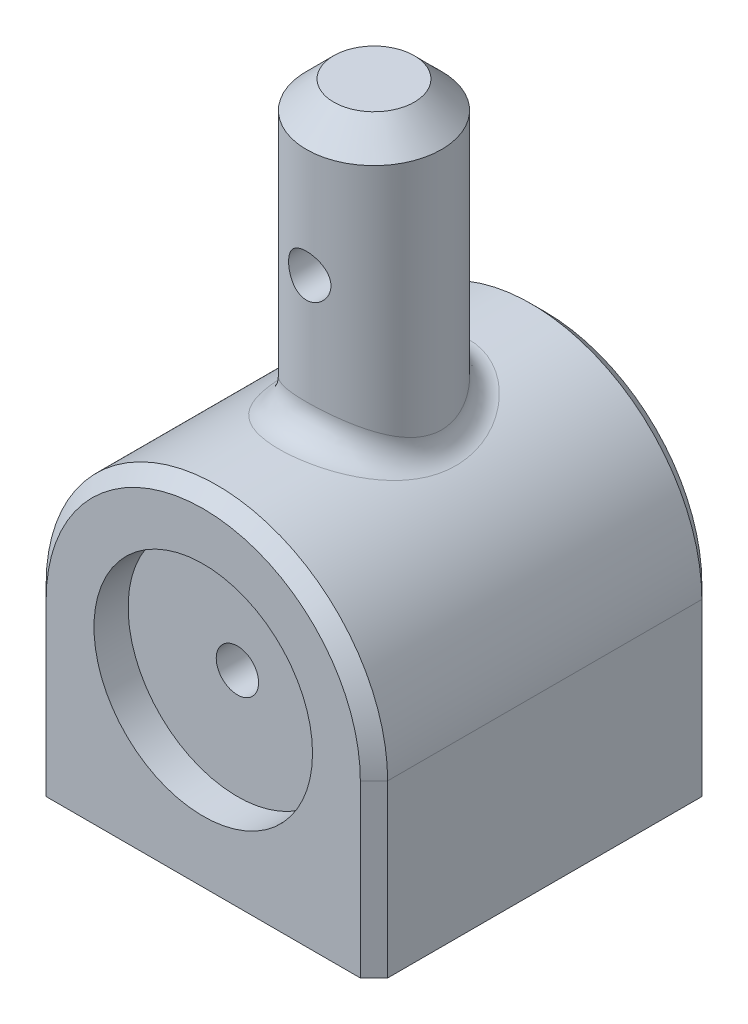
SolidWorks part; units mm, degrees
ref_plane "Front Plane" through (0, 0, 0) normal (0, 0, 1) x (1, 0, 0)
ref_plane "Top Plane" through (0, 0, 0) normal (0, 1, 0) x (1, 0, 0)
ref_plane "Right Plane" through (0, 0, 0) normal (1, 0, 0) x (0, 0, -1)
sketch "Base" plane through (0, 0, 0) normal (0, 0, 1) x (1, 0, 0)
  line L0 (-12.5, 0) -> (16.732, 0) construction
  line L1 (-12.5, 12.5) -> (12.5, 12.5)
  line L2 (-12.5, 12.5) -> (-12.5, -12.5)
  line L3 (-12.5, -12.5) -> (12.5, -12.5)
  line L4 (12.5, 12.5) -> (12.5, -12.5)
  line L5 (-12.5, 12.5) -> (12.5, -12.5) construction
  line L6 (-12.5, -12.5) -> (12.5, 12.5) construction
  line L7 (0, -3.7802) -> (0, 5.268) construction
  arc A0 (-12.5, 0) -> (12.5, 0) centre (0, 0) cw
  circle A1 centre (0, 0) radius 8
  circle A2 centre (0, 0) radius 2.45
  circle A3 centre (0, 0) radius 1.55
  point P0 (0, 0)
  dimension "D2" = 16
  dimension "D3" = 4.9
  dimension "D4" = 3.1
  dimension "D1" = 25
extrude "Boss-Extrude1" add sketch "Base" along normal blind 25 contours A0 L2 L3 L4 | A1 A2 | A2 region at (8.5888, 8.5888, 0) region at (-7.7737, 0, 0) region at (-2.3807, 0, 0)
ref_plane "Mid_Plane" through (0, 0, 12.5) normal (0, 0, -1) x (-1, 0, 0)
extrude "Cut-Extrude1" cut sketch "Base<3>" along normal blind 2.5 contours A1 A2 | A2 region at (-7.7737, 0, 0)
sketch "Base<3>" plane through (0, 0, 0) normal (0, 0, 1) x (1, 0, 0) same geometry as "Base"
ref_plane "Top_Plane" through (0, 12.5, 0) normal (0, 1, 0) x (1, 0, 0)
sketch "Connector_Base" plane through (0, 12.5, 0) normal (0, 1, 0) x (1, 0, 0)
  line L0 (0, 4.6639) -> (0, -18.6282) construction
  line L3 (0, 0) -> (0, -25) construction
  line L4 (-12.5, -25) -> (12.5, -25) construction
  circle A0 centre (0, -12.5) radius 4.95
  point P1 (0, 0)
  point P9 (0, -12.5)
  dimension "D1" = 9.9
extrude "Boss-Extrude7" add sketch "Connector_Base" along normal blind 30 from offset 10 contours A0 region at (0, 12.5, 12.5) offset against normal yes
ref_plane "Screw_Hole_Ref" through (0, 0, 7.55) normal (0, 0, -1) x (-1, 0, 0)
sketch "Sketch5" plane through (0, 0, 7.55) normal (0, 0, -1) x (-1, 0, 0)
  line L0 (0, 12.5) -> (0, 32.5) construction
  circle A0 centre (0, 22.5) radius 1.55
  dimension "D2" = 3.1
extrude "Cut-Extrude2" cut sketch "Sketch5" against normal blind 45
mirror "Mirror2" about plane through (0, 0, 12.5) normal (0, 0, -1) of "Cut-Extrude1"
fillet "Fillet5" radius 2 1 edges at (-0.7257, 12.4789, 17.3965)
chamfer "Chamfer1" distance 2 angle 45 1 edges at (0, 32.5, 17.45)
chamfer "Chamfer2" distance 1 angle 45 6 edges at (-12.5, -6.25, 0) (0, 12.5, 0) (12.5, -6.25, 0) (12.5, -6.25, 25) (0, 12.5, 25) (-12.5, -6.25, 25)
equation "\"Connector_Size\"=25"
equation "\"D1@Base\" = \"Connector_Size\""
equation "\"Bearing_Size\"=16"
equation "\"D2@Base\" = \"Bearing_Size\""
equation "\"Bore_Size\"=5"
equation "\"D3@Base\" = \"Bore_Size\" - 0.1"
equation "\"Screw_Size\"= 3.0"
equation "\"D4@Base\" = \"Screw_Size\" + 0.1"
equation "\"Connector_To_Base_Radius\"= 10mm"
equation "\"D1@Connector_Base\" = \"Connector_To_Base_Radius\" - 0.1"
equation "\"D1@Boss-Extrude7\"= 30"
equation "\"D1@Sketch5\"=10mm"
